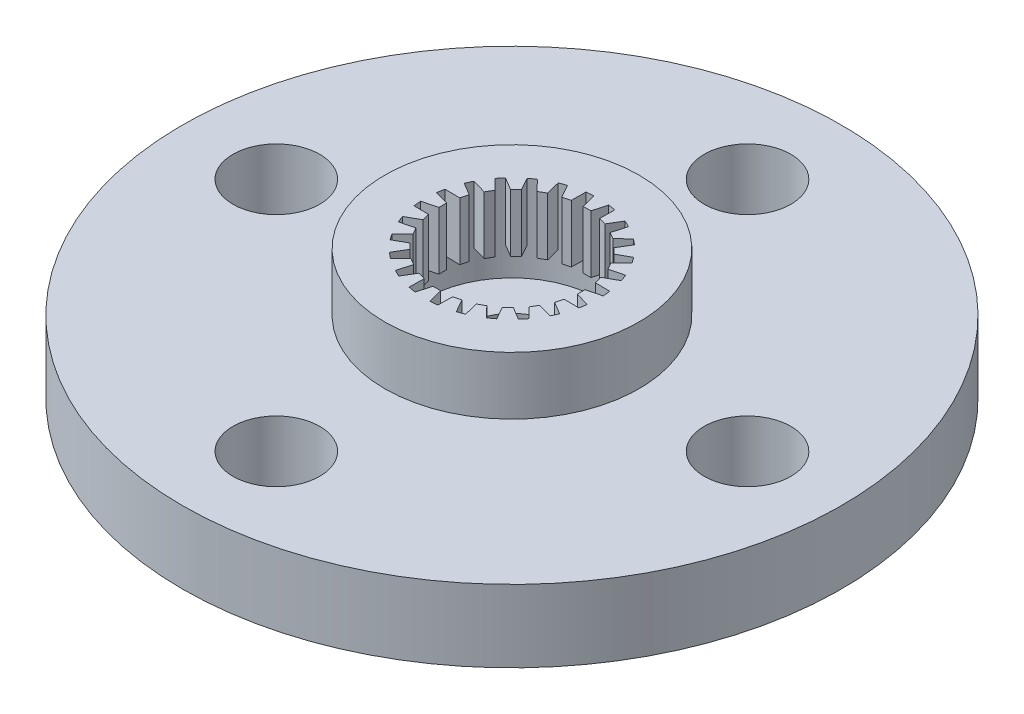
SolidWorks part; units mm, degrees
ref_plane "前视基准面" through (0, 0, 0) normal (0, 0, 1) x (1, 0, 0)
ref_plane "上视基准面" through (0, 0, 0) normal (0, 1, 0) x (1, 0, 0)
ref_plane "右视基准面" through (0, 0, 0) normal (1, 0, 0) x (0, 0, -1)
sketch "草图4" plane through (0, 0, 0) normal (0, 1, 0) x (1, 0, 0)
  circle A0 centre (0, 0) radius 11.4
  dimension "D1" = 22.8
extrude "凸台-拉伸2" add sketch "草图4" along normal blind 2.5
ref_plane "基准面7" through (0, 2.5, 0) normal (0, 1, 0) x (1, 0, 0)
sketch "草图6" plane through (0, 2.5, 0) normal (0, 1, 0) x (1, 0, 0)
  circle A0 centre (0, 0) radius 8.15 construction
  circle A1 centre (0, 8.15) radius 1.5
  circle A2 centre (0, 0) radius 1.5
  circle A3 centre (8.15, 0) radius 1.5
  circle A4 centre (-8.15, 0) radius 1.5
  circle A5 centre (0, -8.15) radius 1.5
  dimension "D1" = 3
  dimension "D2" = 3
  dimension "D3" = 3
  dimension "D4" = 3
  dimension "D5" = 3
  dimension "D6" = 16.3
extrude "切除-拉伸9" cut sketch "草图6" against normal blind 2.5
sketch "草图7" plane through (0, 2.5, 0) normal (0, 1, 0) x (1, 0, 0)
  circle A0 centre (0, 0) radius 4.4
  dimension "D1" = 8.8
extrude "凸台-拉伸3" add sketch "草图7" along normal blind 2
ref_plane "基准面8" through (0, 4.5, 0) normal (0, 1, 0) x (1, 0, 0)
sketch "草图8" plane through (0, 4.5, 0) normal (0, 1, 0) x (1, 0, 0)
  circle A0 centre (0, 0) radius 3
  dimension "D1" = 6
extrude "切除-拉伸10" cut sketch "草图8" against normal blind 3
ref_axis "基准轴1" through (0, 1.5, 0) along (0, 1, 0)
sketch "草图14" plane through (0, 4.5, 0) normal (0, 1, 0) x (1, 0, 0)
  line L0 (2.9769, -0.3715) -> (2.4958, -0.2354)
  line L1 (2.4958, -0.2354) -> (2.4958, 0.0323)
  line L2 (2.4958, 0.0323) -> (2.9958, 0.1588)
  arc A0 (2.9769, -0.3715) -> (2.9958, 0.1588) centre (0, 0) ccw
  dimension "D3" = 3
  dimension "D1" = 30
  dimension "D2" = 0.5
  dimension "0.5" = 0.5
extrude "凸台-拉伸5" add sketch "草图14" against normal blind 2
pattern_circular "阵列(圆周)1" count 24 every 15 about axis through (0, 4.5, 0) along (0, 1, 0) of "凸台-拉伸5"
